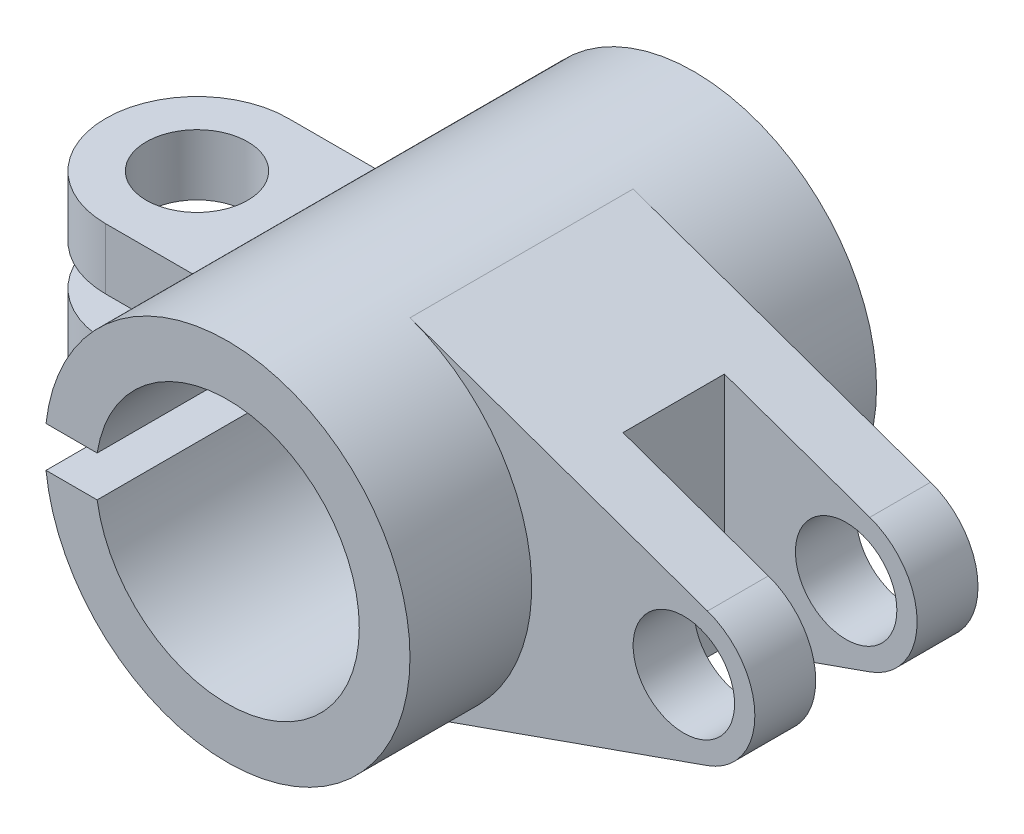
SolidWorks part; units mm, degrees
ref_plane "Front Plane" through (0, 0, 0) normal (0, 0, 1) x (1, 0, 0)
ref_plane "Top Plane" through (0, 0, 0) normal (0, 1, 0) x (1, 0, 0)
ref_plane "Right Plane" through (0, 0, 0) normal (1, 0, 0) x (0, 0, -1)
sketch "Sketch1" plane through (0, 0, 0) normal (0, 0, 1) x (1, 0, 0)
  line L0 (-12.8452, 2) -> (-17.8885, 2)
  line L1 (35.3333, 6.5997) -> (6, 16.9706)
  line L2 (-12.8452, -2) -> (-17.8885, -2)
  line L3 (35.3333, -6.5997) -> (6, -16.9706)
  line L4 (-17.8885, 2) -> (-35, 2)
  line L5 (-35, 2) -> (-35, 8)
  line L6 (-35, 8) -> (-16.1245, 8)
  line L7 (0, 0) -> (-63.9499, 0) construction
  line L8 (-17.8885, -2) -> (-35, -2)
  line L9 (-35, -2) -> (-35, -8)
  line L10 (-35, -8) -> (-16.1245, -8)
  line L11 (21, 11.6673) -> (21, -11.6673)
  arc A0 (-17.8885, -2) -> (-17.8885, 2) centre (0, 0) ccw
  arc A1 (-12.8452, -2) -> (-12.8452, 2) centre (0, 0) ccw
  circle A2 centre (33, 0) radius 5
  arc A3 (35.3333, -6.5997) -> (35.3333, 6.5997) centre (33, 0) ccw
  dimension "D1" = 26
  dimension "D2" = 36
  dimension "D5" = 10
  dimension "D6" = 14
  dimension "D3" = 6
  dimension "D4" = 2
  dimension "D7" = 33
  dimension "D8" = 35
  dimension "D9" = 12
extrude "Boss-Extrude1" add sketch "Sketch1" along normal blind 46 contours A1 L2 A0 L0 region at (-15.3669, 2.5083, 0)
extrude "Boss-Extrude2" add sketch "Sketch1<3>" along normal blind 6 from offset 12 contours L3 A3 L1 A0 A2 region at (27.5339, 0, 0)
sketch "Sketch1<3>" plane through (0, 0, 0) normal (0, 0, 1) x (1, 0, 0) same geometry as "Sketch1"
extrude "Boss-Extrude3" add sketch "Sketch1<4>" along normal blind 6 from offset 28 contours L3 A3 L1 A0 A2 region at (27.5339, 0, 0)
sketch "Sketch1<4>" plane through (0, 0, 0) normal (0, 0, 1) x (1, 0, 0) same geometry as "Sketch1"
extrude "Boss-Extrude4" add sketch "Sketch1<5>" along normal blind 18 from offset 14 contours A0 L6 L5 L4 | A0 L8 L9 L10 region at (-26.0911, 5.0492, 0) region at (-26.0911, -5.0492, 0)
sketch "Sketch1<5>" plane through (0, 0, 0) normal (0, 0, 1) x (1, 0, 0) same geometry as "Sketch1"
fillet "Fillet2" 2 edges at (-35, 5, 32) (-35, 5, 14) type full round first side face at (-26.0689, 5.0193, 32) second side face at (-26.0689, 5.0193, 14) middle face at (-35, 5, 23)
fillet "Fillet3" 2 edges at (-35, -5, 32) (-35, -5, 14) type full round first side face at (-26.0689, -5.0193, 32) second side face at (-26.0689, -5.0193, 14) middle face at (-35, -5, 23)
hole_wizard "Ø10.0mm Dowel Hole1" positions "3DSketch2" profile "Sketch2" hole size "Ø10.0" standard "AS"
sketch3d "3DSketch2"
  line L0 (-26, 2, 23) -> (-26, 8, 23) construction
  point P0 (-26, 8, 23)
sketch "Sketch2" plane through (-26, 8, 23) normal (1, 0, 0) x (0, 0, 1)
  line L0 (0, 0) -> (0, 33.0043)
  line L1 (0, 33.0043) -> (5, 30)
  line L2 (5, 30) -> (5, 0)
  line L5 (5, 0) -> (0, 0)
  line L10 (0, 33.0043) -> (-5, 30) construction
  line L11 (0, -6.35) -> (0, 107.95) construction
  dimension "Hole Dia." = 10
  dimension "Hole Depth" = 30
  dimension "Drill Angle" = 118
extrude "Boss-Extrude5" add sketch "Sketch1<6>" along normal blind 22 from offset 12 contours A0 L3 L11 L1 region at (13.3763, 13.9691, 0)
sketch "Sketch1<6>" plane through (0, 0, 0) normal (0, 0, 1) x (1, 0, 0) same geometry as "Sketch1"
